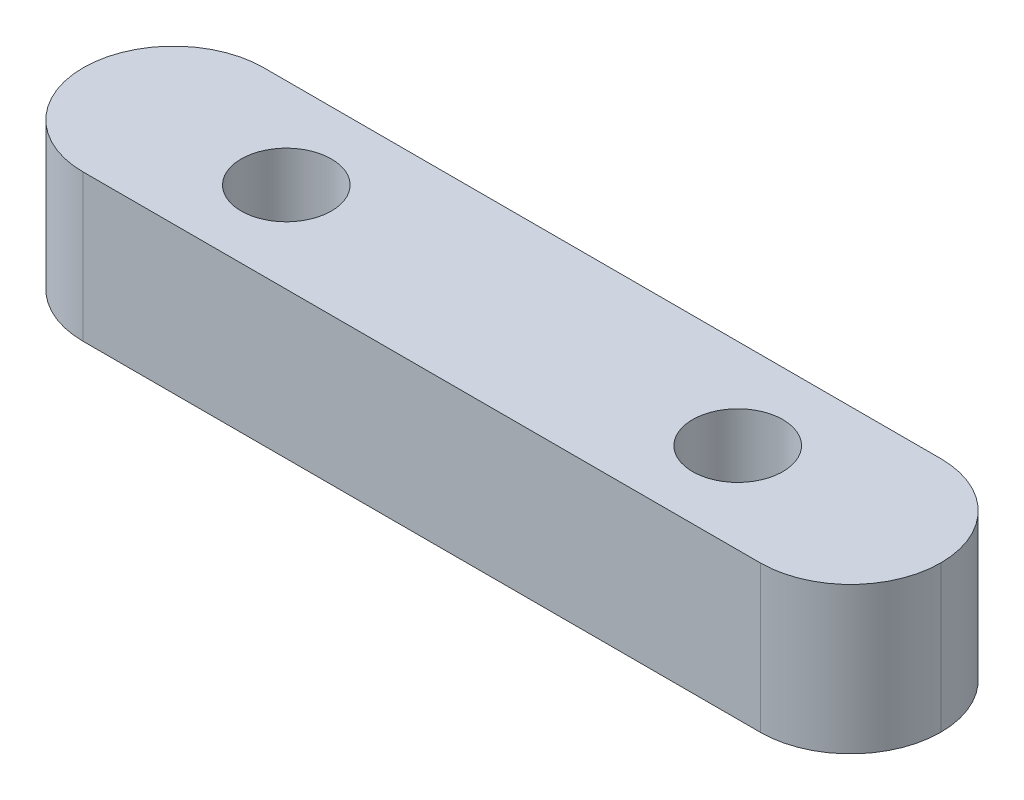
SolidWorks part; units mm, degrees
material "PETG-cf"
ref_plane "Plano frontal" through (0, 0, 0) normal (0, 0, 1) x (1, 0, 0)
ref_plane "Plano superior" through (0, 0, 0) normal (0, 1, 0) x (1, 0, 0)
ref_plane "Plano direito" through (0, 0, 0) normal (1, 0, 0) x (0, 0, -1)
sketch "Esboço1" plane through (0, 0, 0) normal (0, 1, 0) x (1, 0, 0)
  line L0 (-19, 0) -> (19, 0) construction
  line L1 (-19, -4) -> (19, -4)
  line L2 (-19, -4) -> (-19, 4)
  line L3 (-19, 4) -> (19, 4)
  line L4 (19, -4) -> (19, 4)
  line L5 (-19, -4) -> (19, 4) construction
  line L6 (-19, 4) -> (19, -4) construction
  line L7 (0, 4) -> (0, -4) construction
  circle A0 centre (-10, 0) radius 2
  circle A1 centre (10, 0) radius 2
  point P0 (0, 0)
  dimension "D3" = 4
  dimension "D1" = 38
  dimension "D2" = 8
  dimension "D4" = 20
extrude "Ressalto-extrusão1" add sketch "Esboço1" along normal mid plane 6.5
fillet "Filete1" radius 4 4 edges at (-19, 0, 4) (-19, 0, -4) (19, 0, -4) (19, 0, 4)
move or copy body "Corpo-Converter em corpo de malha1" [suppressed] bodies to move or copy 101 copy no translate (0, 0, 0) parameters "D1"=0, "D2"=0, "D3"=0
